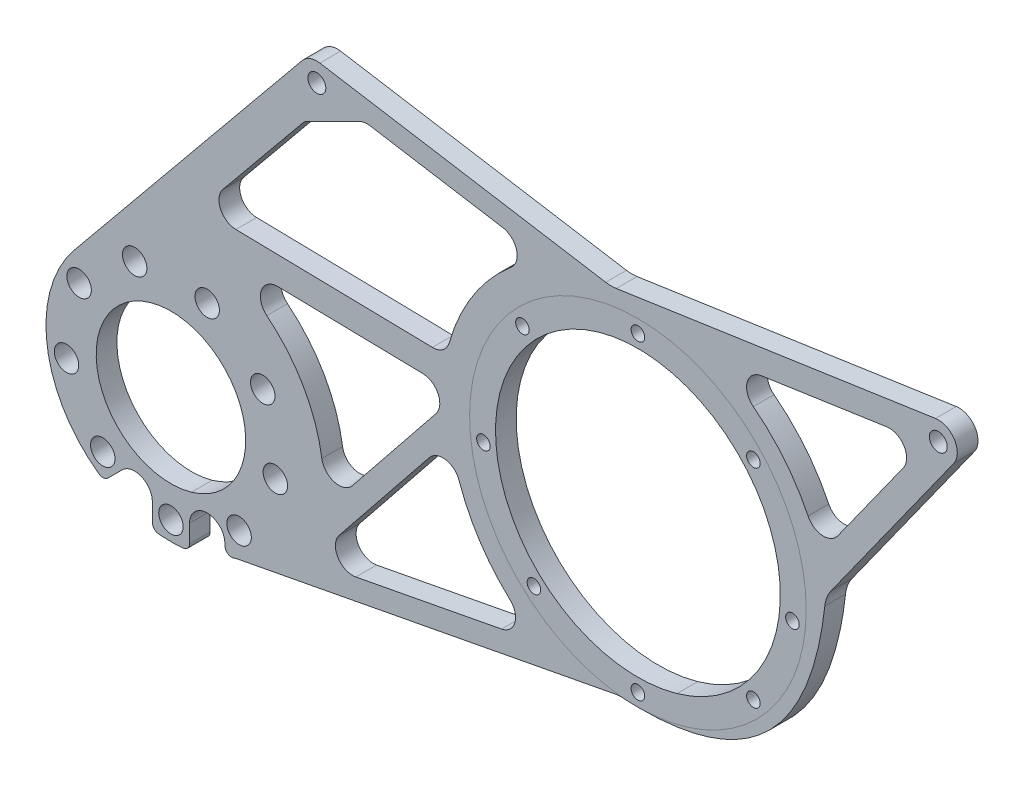
SolidWorks part; units mm, degrees
material "6061-T6 (SS)"
ref_plane "X-Y Datum" through (0, 0, 0) normal (0, 0, 1) x (1, 0, 0)
ref_plane "X-Z Datum" through (0, 0, 0) normal (0, 1, 0) x (1, 0, 0)
ref_plane "Y-Z Datum" through (0, 0, 0) normal (1, 0, 0) x (0, 0, -1)
sketch "Sketch15" plane through (0, 0, 0) normal (0, 0, 1) x (-1, 0, 0)
  line L0 (-666.75, 77.9015) -> (-548.64, 0) construction
  line L1 (-666.75, 77.9015) -> (-494.9785, 127) construction
  line L8 (-471.7786, 164.3167) -> (-477.0435, 159.0518)
  line L9 (-488.1397, 163.648) -> (-488.1397, 170.2207)
  line L10 (-501.8173, 170.2207) -> (-501.8173, 163.648)
  line L11 (-514.8173, 163.648) -> (-514.8173, 164.225)
  line L17 (-660.4, 0) -> (-548.64, 0)
  line L18 (-777.24, 0) -> (-660.4, 0)
  line L19 (-777.24, 145.034) -> (-777.24, 0)
  line L20 (-789.94, 132.334) -> (-764.54, 157.734)
  line L21 (-789.94, 157.734) -> (-764.54, 132.334)
  line L22 (-789.94, 132.334) -> (-764.54, 132.334)
  line L23 (-789.94, 157.734) -> (-764.54, 157.734)
  line L24 (-789.94, 157.734) -> (-789.94, 132.334)
  line L25 (-764.54, 157.734) -> (-764.54, 132.334)
  line L26 (-543.2372, -4.4272) -> (-459.4185, 97.8608)
  line L27 (-777.24, -6.985) -> (-548.64, -6.985)
  line L28 (-784.225, 0) -> (-784.225, 145.034)
  line L29 (-776.4928, 151.9789) -> (-660.1268, 139.4587)
  line L30 (-660.1268, 139.4587) -> (-518.666, 166.4019)
  circle A1 centre (-666.75, 77.9015) radius 52.3875
  circle A4 centre (-548.64, 0) radius 12.7
  circle A5 centre (-777.24, 0) radius 12.7
  arc A16 (-518.666, 166.4019) -> (-468.5208, 164.5979) centre (-494.9785, 127) ccw
  arc A17 (-468.5208, 164.5979) -> (-471.7786, 164.3167) centre (-469.9826, 162.5207) ccw
  arc A18 (-488.1397, 163.648) -> (-477.0435, 159.0518) centre (-481.6397, 163.648) ccw
  arc A19 (-488.1397, 170.2207) -> (-490.4283, 172.7483) centre (-490.6797, 170.2207) ccw
  arc A20 (-490.4283, 172.7483) -> (-499.5287, 172.7483) centre (-494.9785, 127) ccw
  arc A21 (-499.5287, 172.7483) -> (-501.8173, 170.2207) centre (-499.2773, 170.2207) ccw
  arc A22 (-514.8173, 163.648) -> (-501.8173, 163.648) centre (-508.3173, 163.648) ccw
  arc A23 (-514.8173, 164.225) -> (-518.666, 166.4019) centre (-517.3573, 164.225) ccw
  circle A30 centre (-709.2207, 116.1423) radius 2.5
  circle A31 centre (-624.2793, 39.6607) radius 2.5
  circle A33 centre (-709.2207, 39.6607) radius 2.5
  circle A34 centre (-723.5869, 83.8753) radius 2.5
  circle A35 centre (-609.9131, 83.8753) radius 2.5
  circle A36 centre (-666.75, 20.7515) radius 2.5
  arc A40 (-666.75, 132.5515) -> (-666.75, 137.5515) centre (-666.75, 135.0515) ccw
  arc A41 (-666.75, 137.5515) -> (-666.75, 132.5515) centre (-666.75, 135.0515) ccw
  circle A43 centre (-628.5092, 120.3722) radius 2.5
  circle A45 centre (-666.75, 77.9015) radius 61.9125
  circle A46 centre (-548.64, 0) radius 3.3
  circle A47 centre (-777.24, 0) radius 3.3
  circle A48 centre (-777.24, 145.034) radius 3.3
  circle A49 centre (-548.64, 0) radius 6.985
  circle A50 centre (-777.24, 0) radius 6.985
  circle A51 centre (-777.24, 145.034) radius 6.985
  circle A61 centre (-461.2035, 107.5) radius 4.5
  circle A62 centre (-481.6397, 90.352) radius 4.5
  circle A63 centre (-508.3173, 90.352) radius 4.5
  circle A64 centre (-528.7535, 107.5) radius 4.5
  circle A65 centre (-533.386, 133.7723) radius 4.5
  circle A66 centre (-520.0472, 156.8757) radius 4.5
  circle A67 centre (-494.9785, 166) radius 4.5
  circle A68 centre (-469.9098, 156.8757) radius 4.5
  circle A69 centre (-456.571, 133.7723) radius 4.5
  circle A71 centre (-494.9785, 127) radius 27.4955
  dimension "D2" = 6.6
  dimension "D3" = 6.6
  dimension "D4" = 6.6
  dimension "D5" = 13.97
  dimension "D6" = 13.97
  dimension "D7" = 13.97
  dimension "D1" = 141.4871
extrude "Boss-Extrude1" add sketch "Sketch15" along normal blind 7.62 contours A45 A1 A30 A31 A33 A34 A35 A36 A41 A40 A43 | L30 A45 L29 L25 L22 L19 A5 L18 L17 A4 L26 A16 | A51 L21 L25 L29 L20 | A51 L19 L22 L21 | L19 A51 L21 A48 | L20 A51 L19 A48 | A51 L28 L20 | A51 L20 L28 L22 L19 | L21 A51 L20 A48 | A51 L20 A48 L21 | L20 A51 L21 A48 | A51 L20 L29 | A5 L19 L22 L28 | A50 L19 A5 L28 | A50 L18 A5 L19 | A50 L27 A5 L18 | A50 L18 A47 L19 | L18 A50 L19 A47 | A5 L27 A4 L17 L18 | A49 L17 A4 L27 | A49 L26 A4 L17 | A49 A46 | L11 A23 A16 A17 L8 A18 L9 A19 A20 A21 L10 A22 A71 A69 A68 A67 A66 A65 A64 A63 A62 A61 region at (470.0892, -163.7557, 0) region at (621.9919, -118.1022, 0) region at (500.7414, -53.0926, 0) region at (540.1092, 0.1341, 0) region at (545.7357, 6.1347, 0) region at (662.94, 3.5042, 0) region at (557.2397, 3.7525, 0) region at (767.6155, -143.202, 0) region at (768.6403, 3.7525, 0) region at (770.798, -6.442, 0) region at (772.2286, -135.2354, 0) region at (772.7928, -151.1055, 0) region at (782.0394, 4.7994, 0) region at (780.9925, -8.5997, 0) region at (780.7424, -72.1789, 0) region at (773.8261, -3.4139, 0) region at (775.2402, -140.206, 0) region at (772.412, -145.034, 0) region at (780.8486, -135.5958, 0) region at (777.24, -149.862, 0) region at (782.068, -145.034, 0) region at (779.2398, -140.206, 0) region at (783.5955, -140.54, 0)
ref_point "Point1"
ref_point "Point2"
ref_plane "Plane1" through (666.75, -77.9015, 0) normal (-0.9615, -0.2748, 0) x (0, 0, 1)
ref_plane "Plane2" through (494.9785, -127, 0) normal (0.9615, 0.2748, 0) x (0, 0, -1)
split line "Split Line1"
split line "Split Line2"
sketch "Sketch17" plane through (0, 0, 7.62) normal (0, 0, 1) x (1, 0, 0)
  circle A0 centre (666.75, -77.9015) radius 61.9125 construction
  circle A1 centre (666.75, -77.9015) radius 61.9125
split line "Split Line3"
ref_axis "Axis4" through (666.75, -77.9015, 7.62) along (0, 0, -1)
ref_axis "Axis5" through (494.9785, -127, 7.62) along (0, 0, -1)
sketch "Sketch18" plane through (0, 0, 7.62) normal (0, 0, 1) x (1, 0, 0)
  line L4 (514.8173, -163.648) -> (514.8173, -164.225)
  line L5 (501.8173, -170.2207) -> (501.8173, -163.648)
  line L6 (488.1397, -163.648) -> (488.1397, -170.2207)
  line L7 (471.7786, -164.3167) -> (477.0435, -159.0518)
  line L8 (514.8173, -163.648) -> (514.8173, -164.225)
  line L9 (501.8173, -170.2207) -> (501.8173, -163.648)
  line L10 (488.1397, -163.648) -> (488.1397, -170.2207)
  line L11 (471.7786, -164.3167) -> (477.0435, -159.0518)
  line L12 (735.8271, -69.9563) -> (782.9228, -4.0616)
  line L13 (735.8271, -69.9563) -> (783.0611, -141.1732)
  line L14 (776.2216, 6.9104) -> (656.8438, -10.6825)
  line L15 (656.8438, -10.6825) -> (549.7714, 6.8928)
  line L16 (776.4928, -151.9789) -> (687.9549, -142.4528)
  line L17 (776.4928, -151.9789) -> (660.1268, -139.4587) construction
  line L18 (543.2372, 4.4272) -> (459.4185, -97.8608) construction
  line L19 (543.2372, 4.4272) -> (459.4185, -97.8608)
  line L20 (660.1268, -139.4587) -> (518.666, -166.4019) construction
  line L21 (660.1268, -139.4587) -> (518.666, -166.4019)
  circle A0 centre (666.75, -77.9015) radius 67.945
  circle A1 centre (666.75, -77.9015) radius 52.3875
  circle A2 centre (666.75, -77.9015) radius 52.3875
  circle A3 centre (548.64, 0) radius 12.7
  circle A4 centre (548.64, 0) radius 12.7
  circle A5 centre (777.24, 0) radius 12.7
  circle A6 centre (777.24, 0) radius 12.7
  circle A7 centre (777.24, 0) radius 6.985 construction
  circle A8 centre (777.24, -145.034) radius 6.985 construction
  circle A9 centre (548.64, 0) radius 6.985 construction
  arc A10 (514.8173, -164.225) -> (518.666, -166.4019) centre (517.3573, -164.225) ccw
  arc A11 (514.8173, -163.648) -> (501.8173, -163.648) centre (508.3173, -163.648) ccw
  arc A12 (499.5287, -172.7483) -> (501.8173, -170.2207) centre (499.2773, -170.2207) ccw
  arc A13 (490.4283, -172.7483) -> (499.5287, -172.7483) centre (494.9785, -127) ccw
  arc A14 (488.1397, -170.2207) -> (490.4283, -172.7483) centre (490.6797, -170.2207) ccw
  arc A15 (488.1397, -163.648) -> (477.0435, -159.0518) centre (481.6397, -163.648) ccw
  arc A16 (468.5208, -164.5979) -> (471.7786, -164.3167) centre (469.9826, -162.5207) ccw
  arc A17 (518.666, -166.4019) -> (468.5208, -164.5979) centre (494.9785, -127) ccw
  arc A18 (514.8173, -164.225) -> (518.666, -166.4019) centre (517.3573, -164.225) ccw
  arc A19 (514.8173, -163.648) -> (501.8173, -163.648) centre (508.3173, -163.648) ccw
  arc A20 (499.5287, -172.7483) -> (501.8173, -170.2207) centre (499.2773, -170.2207) ccw
  arc A21 (490.4283, -172.7483) -> (499.5287, -172.7483) centre (494.9785, -127) ccw
  arc A22 (488.1397, -170.2207) -> (490.4283, -172.7483) centre (490.6797, -170.2207) ccw
  arc A23 (488.1397, -163.648) -> (477.0435, -159.0518) centre (481.6397, -163.648) ccw
  arc A24 (468.5208, -164.5979) -> (471.7786, -164.3167) centre (469.9826, -162.5207) ccw
  arc A25 (518.666, -166.4019) -> (468.5208, -164.5979) centre (494.9785, -127) ccw
  circle A26 centre (777.24, -145.034) radius 6.985
  circle A27 centre (777.24, 0) radius 6.985
  circle A28 centre (548.64, 0) radius 6.985
  circle A29 centre (666.75, -77.9015) radius 69.5325
  circle A30 centre (666.75, -77.9015) radius 61.9125 construction
  point P56 (735.8271, -69.9563)
  line M37 (784.225, -145.034) -> (784.225, 0)
  line M39 (777.24, 6.985) -> (548.64, 6.985)
  dimension "D5" = 135.89
  dimension "D7" = 7.62
  dimension "D6" = 69.9563
  dimension "D1" = 0
  dimension "D2" = 0
  dimension "D3" = 0
  dimension "D4" = 0
extrude "Profile" cut sketch "Sketch18" against normal through all contours A6 A4 L15 L14 M39 | A28 L15 A4 M39 | A27 A6 L14 M39 | A26 A6 L12 L13 M37 | A27 L12 A6 M37 | L14 A29 L15 region at (660.8946, -9.368, 7.62) region at (660.9592, 1.1518, 7.62) region at (556.2469, 6.3803, 7.62) region at (769.684, 6.4437, 7.62) region at (767.9562, -72.3588, 7.62) region at (781.6609, -8.7245, 7.62)
fillet "Prof Fillet" radius 12.7 2 edges at (660.1268, -139.4587, 3.81) (656.8438, -10.6825, 3.81)
sketch "Sketch19" plane through (0, 0, 7.62) normal (0, 0, 1) x (1, 0, 0)
  line L0 (733.3947, -58.0707) -> (773.0846, -2.538)
  line L1 (773.0846, -2.538) -> (694.453, -14.126)
  line L2 (776.2216, 6.9104) -> (658.8007, -10.3941) construction
  line L3 (735.8271, -69.9563) -> (782.9228, -4.0616) construction
  line L4 (514.8173, -163.648) -> (514.8173, -164.225)
  line L5 (501.8173, -170.2207) -> (501.8173, -163.648)
  line L6 (488.1397, -163.648) -> (488.1397, -170.2207)
  line L7 (471.7786, -164.3167) -> (477.0435, -159.0518)
  line L8 (514.8173, -163.648) -> (514.8173, -164.225)
  line L9 (501.8173, -170.2207) -> (501.8173, -163.648)
  line L10 (488.1397, -163.648) -> (488.1397, -170.2207)
  line L11 (471.7786, -164.3167) -> (477.0435, -159.0518)
  line L12 (735.5557, -87.9288) -> (772.6812, -143.9048)
  line L13 (772.6812, -143.9048) -> (704.1334, -136.5295)
  line L14 (735.8271, -69.9563) -> (783.0611, -141.1732) construction
  line L15 (776.4928, -151.9789) -> (660.1268, -139.4587) construction
  arc A0 (694.453, -14.126) -> (733.3947, -58.0707) centre (666.75, -77.9015) cw
  circle A1 centre (666.75, -77.9015) radius 52.3875
  circle A2 centre (666.75, -77.9015) radius 52.3875
  circle A3 centre (548.64, 0) radius 12.7
  circle A4 centre (548.64, 0) radius 12.7
  circle A5 centre (777.24, 0) radius 12.7
  circle A6 centre (777.24, 0) radius 12.7
  circle A7 centre (666.75, -77.9015) radius 61.9125 construction
  arc A8 (704.1334, -136.5295) -> (735.5557, -87.9288) centre (666.75, -77.9015) ccw
  arc A10 (514.8173, -164.225) -> (518.666, -166.4019) centre (517.3573, -164.225) ccw
  arc A11 (514.8173, -163.648) -> (501.8173, -163.648) centre (508.3173, -163.648) ccw
  arc A12 (499.5287, -172.7483) -> (501.8173, -170.2207) centre (499.2773, -170.2207) ccw
  arc A13 (490.4283, -172.7483) -> (499.5287, -172.7483) centre (494.9785, -127) ccw
  arc A14 (488.1397, -170.2207) -> (490.4283, -172.7483) centre (490.6797, -170.2207) ccw
  arc A15 (488.1397, -163.648) -> (477.0435, -159.0518) centre (481.6397, -163.648) ccw
  arc A16 (468.5208, -164.5979) -> (471.7786, -164.3167) centre (469.9826, -162.5207) ccw
  arc A17 (518.666, -166.4019) -> (468.5208, -164.5979) centre (494.9785, -127) ccw
  arc A18 (514.8173, -164.225) -> (518.666, -166.4019) centre (517.3573, -164.225) ccw
  arc A19 (514.8173, -163.648) -> (501.8173, -163.648) centre (508.3173, -163.648) ccw
  arc A20 (499.5287, -172.7483) -> (501.8173, -170.2207) centre (499.2773, -170.2207) ccw
  arc A21 (490.4283, -172.7483) -> (499.5287, -172.7483) centre (494.9785, -127) ccw
  arc A22 (488.1397, -170.2207) -> (490.4283, -172.7483) centre (490.6797, -170.2207) ccw
  arc A23 (488.1397, -163.648) -> (477.0435, -159.0518) centre (481.6397, -163.648) ccw
  arc A24 (468.5208, -164.5979) -> (471.7786, -164.3167) centre (469.9826, -162.5207) ccw
  arc A25 (518.666, -166.4019) -> (468.5208, -164.5979) centre (494.9785, -127) ccw
  dimension "D7" = 7.62
  dimension "D8" = 7.62
  dimension "D5" = 8.89
  dimension "D6" = 8.89
  dimension "D9" = 10.16
  dimension "D10" = 7.62
  dimension "D1" = 0
  dimension "D2" = 0
  dimension "D3" = 0
  dimension "D4" = 0
extrude "Cut-Extrude2" cut sketch "Sketch19" against normal through all contours L1 A0 L0 | A8 L13 L12 | L1 A6 L0 | L13 A8 L12 region at (735.848, -23.7543, 7.62) region at (768.7055, -5.2125, 7.62) region at (739.9333, -124.2564, 7.62)
fillet "Fillet2" radius 6.35 6 edges at (694.453, -14.126, 3.81) (773.0846, -2.538, 3.81) (733.3947, -58.0707, 3.81) (772.6812, -143.9048, 3.81) (704.1334, -136.5295, 3.81) (735.5557, -87.9288, 3.81)
sketch "Sketch22" plane through (0, 0, 7.62) normal (0, 0, 1) x (1, 0, 0)
  line L0 (632.6117, -14.4269) -> (566.1379, -3.5157)
  line L1 (566.1379, -3.5157) -> (544.2067, -14.4269)
  line L2 (654.892, -10.3621) -> (549.7714, 6.8928) construction
  line L4 (514.8173, -163.648) -> (514.8173, -164.225)
  line L5 (501.8173, -170.2207) -> (501.8173, -163.648)
  line L6 (488.1397, -163.648) -> (488.1397, -170.2207)
  line L7 (471.7786, -164.3167) -> (477.0435, -159.0518)
  line L8 (514.8173, -163.648) -> (514.8173, -164.225)
  line L9 (501.8173, -170.2207) -> (501.8173, -163.648)
  line L10 (488.1397, -163.648) -> (488.1397, -170.2207)
  line L11 (471.7786, -164.3167) -> (477.0435, -159.0518)
  line L12 (630.6345, -137.319) -> (546.093, -153.4211)
  line L13 (546.093, -153.4211) -> (598.0511, -88.6361)
  line L14 (658.2707, -139.8122) -> (518.666, -166.4019) construction
  line L15 (505.7956, -61.3018) -> (544.2067, -14.4269)
  line L16 (544.2067, -14.4269) -> (632.6117, -14.4269)
  line L17 (596.2144, -63.0967) -> (505.7956, -61.3018)
  line L18 (543.2372, 4.4272) -> (459.4185, -97.8608) construction
  line L19 (502.7234, -71.4029) -> (600.5471, -73.3447)
  line L20 (600.5471, -73.3447) -> (550.4088, -135.8605)
  arc A0 (598.0511, -88.6361) -> (630.6345, -137.319) centre (666.75, -77.9015) ccw
  circle A1 centre (666.75, -77.9015) radius 52.3875
  circle A2 centre (666.75, -77.9015) radius 52.3875
  circle A3 centre (548.64, 0) radius 12.7
  circle A4 centre (548.64, 0) radius 12.7
  circle A5 centre (777.24, 0) radius 12.7
  circle A6 centre (777.24, 0) radius 12.7
  circle A7 centre (666.75, -77.9015) radius 61.9125 construction
  arc A8 (632.6117, -14.4269) -> (596.2144, -63.0967) centre (666.75, -77.9015) ccw
  arc A9 (502.7234, -71.4029) -> (550.4088, -135.8605) centre (494.9785, -127) cw
  arc A10 (514.8173, -164.225) -> (518.666, -166.4019) centre (517.3573, -164.225) ccw
  arc A11 (514.8173, -163.648) -> (501.8173, -163.648) centre (508.3173, -163.648) ccw
  arc A12 (499.5287, -172.7483) -> (501.8173, -170.2207) centre (499.2773, -170.2207) ccw
  arc A13 (490.4283, -172.7483) -> (499.5287, -172.7483) centre (494.9785, -127) ccw
  arc A14 (488.1397, -170.2207) -> (490.4283, -172.7483) centre (490.6797, -170.2207) ccw
  arc A15 (488.1397, -163.648) -> (477.0435, -159.0518) centre (481.6397, -163.648) ccw
  arc A16 (468.5208, -164.5979) -> (471.7786, -164.3167) centre (469.9826, -162.5207) ccw
  arc A17 (518.666, -166.4019) -> (468.5208, -164.5979) centre (494.9785, -127) ccw
  arc A18 (514.8173, -164.225) -> (518.666, -166.4019) centre (517.3573, -164.225) ccw
  arc A19 (514.8173, -163.648) -> (501.8173, -163.648) centre (508.3173, -163.648) ccw
  arc A20 (499.5287, -172.7483) -> (501.8173, -170.2207) centre (499.2773, -170.2207) ccw
  arc A21 (490.4283, -172.7483) -> (499.5287, -172.7483) centre (494.9785, -127) ccw
  arc A22 (488.1397, -170.2207) -> (490.4283, -172.7483) centre (490.6797, -170.2207) ccw
  arc A23 (488.1397, -163.648) -> (477.0435, -159.0518) centre (481.6397, -163.648) ccw
  arc A24 (468.5208, -164.5979) -> (471.7786, -164.3167) centre (469.9826, -162.5207) ccw
  arc A25 (518.666, -166.4019) -> (468.5208, -164.5979) centre (494.9785, -127) ccw
  dimension "D6" = 7.62
  dimension "D7" = 10.16
  dimension "D14" = 10.16
  dimension "D5" = 7.62
  dimension "D8" = 12.7
  dimension "D9" = 7.62
  dimension "D10" = 24.4955
  dimension "D11" = 90.4189
  dimension "D12" = 51.9581
  dimension "D13" = 64.7849
  dimension "D15" = 10.16
  dimension "D16" = 7.62
  dimension "D17" = 1.7949
  dimension "D1" = 0
  dimension "D2" = 0
  dimension "D3" = 0
  dimension "D4" = 0
extrude "Cut-Extrude4" cut sketch "Sketch22" against normal through all contours L1 L16 L0 | L1 A4 | L17 L15 L16 A8 | L20 A9 L19 | L13 A0 L12 region at (581.8773, -10.8016, 7.62) region at (553.8291, -10.4299, 7.62)
fillet "Fillet5" radius 6.35 11 edges at (630.6345, -137.319, 3.81) (546.093, -153.4211, 3.81) (598.0511, -88.6361, 3.81) (550.4088, -135.8605, 3.81) (600.5471, -73.3447, 3.81) (502.7234, -71.4029, 3.81) (596.2144, -63.0967, 3.81) (505.7956, -61.3018, 3.81) (632.6117, -14.4269, 3.81) (566.1379, -3.5157, 3.81) (544.2067, -14.4269, 3.81)
sketch "Sketch26" plane through (0, 0, 7.62) normal (0, 0, 1) x (1, 0, 0)
  line L0 (776.4928, -151.9789) -> (662.0055, -139.6608) construction
  line L1 (735.8271, -69.9563) -> (783.0611, -141.1732) construction
  line L2 (772.6812, -143.9048) -> (735.5557, -87.9288)
  line L3 (704.1334, -136.5295) -> (772.6812, -143.9048)
  line L4 (488.1397, -163.648) -> (488.1397, -170.2207)
  line L5 (501.8173, -170.2207) -> (501.8173, -163.648)
  line L6 (514.8173, -163.648) -> (514.8173, -164.225)
  line L7 (471.7786, -164.3167) -> (477.0435, -159.0518)
  line L8 (488.1397, -163.648) -> (488.1397, -170.2207)
  line L9 (501.8173, -170.2207) -> (501.8173, -163.648)
  line L10 (514.8173, -163.648) -> (514.8173, -164.225)
  line L11 (471.7786, -164.3167) -> (477.0435, -159.0518)
  line L12 (772.6812, -143.9048) -> (735.5557, -87.9288)
  line L13 (704.1334, -136.5295) -> (772.6812, -143.9048)
  line L14 (733.3947, -58.0707) -> (773.0846, -2.538)
  line L15 (773.0846, -2.538) -> (694.453, -14.126)
  line L16 (733.3947, -58.0707) -> (773.0846, -2.538)
  line L17 (773.0846, -2.538) -> (694.453, -14.126)
  line L18 (776.4928, -151.9789) -> (662.0055, -139.6608)
  line L19 (735.8271, -69.9563) -> (783.0611, -141.1732)
  circle A1 centre (666.75, -77.9015) radius 52.3875
  circle A2 centre (666.75, -77.9015) radius 52.3875
  circle A3 centre (777.24, 0) radius 12.7
  circle A4 centre (777.24, 0) radius 12.7
  circle A5 centre (548.64, 0) radius 12.7
  circle A6 centre (548.64, 0) radius 12.7
  arc A7 (704.1334, -136.5295) -> (735.5557, -87.9288) centre (666.75, -77.9015) ccw
  arc A8 (704.1334, -136.5295) -> (735.5557, -87.9288) centre (666.75, -77.9015) ccw
  arc A9 (733.3947, -58.0707) -> (694.453, -14.126) centre (666.75, -77.9015) ccw
  arc A10 (733.3947, -58.0707) -> (694.453, -14.126) centre (666.75, -77.9015) ccw
  circle A11 centre (666.75, -77.9015) radius 69.5325
  arc A12 (776.4928, -151.9789) -> (783.0611, -141.1732) centre (777.24, -145.034) ccw construction
  arc A13 (776.4928, -151.9789) -> (783.0611, -141.1732) centre (777.24, -145.034) ccw
  arc A14 (488.1397, -170.2207) -> (490.4283, -172.7483) centre (490.6797, -170.2207) ccw
  arc A15 (490.4283, -172.7483) -> (499.5287, -172.7483) centre (494.9785, -127) ccw
  arc A16 (499.5287, -172.7483) -> (501.8173, -170.2207) centre (499.2773, -170.2207) ccw
  arc A17 (514.8173, -163.648) -> (501.8173, -163.648) centre (508.3173, -163.648) ccw
  arc A18 (514.8173, -164.225) -> (518.666, -166.4019) centre (517.3573, -164.225) ccw
  arc A19 (518.666, -166.4019) -> (468.5208, -164.5979) centre (494.9785, -127) ccw
  arc A20 (468.5208, -164.5979) -> (471.7786, -164.3167) centre (469.9826, -162.5207) ccw
  arc A21 (488.1397, -163.648) -> (477.0435, -159.0518) centre (481.6397, -163.648) ccw
  arc A22 (488.1397, -170.2207) -> (490.4283, -172.7483) centre (490.6797, -170.2207) ccw
  arc A23 (490.4283, -172.7483) -> (499.5287, -172.7483) centre (494.9785, -127) ccw
  arc A24 (499.5287, -172.7483) -> (501.8173, -170.2207) centre (499.2773, -170.2207) ccw
  arc A25 (514.8173, -163.648) -> (501.8173, -163.648) centre (508.3173, -163.648) ccw
  arc A26 (514.8173, -164.225) -> (518.666, -166.4019) centre (517.3573, -164.225) ccw
  arc A27 (518.666, -166.4019) -> (468.5208, -164.5979) centre (494.9785, -127) ccw
  arc A28 (468.5208, -164.5979) -> (471.7786, -164.3167) centre (469.9826, -162.5207) ccw
  arc A29 (488.1397, -163.648) -> (477.0435, -159.0518) centre (481.6397, -163.648) ccw
  spline S0 degree 2 poles (662.0055, -139.6608) (729.1997, -143.0989) (735.8271, -69.9563) knots 0 0 0 1 1 1
  dimension "D7" = 115.4464
  dimension "D8" = 44.8387
  dimension "D1" = 0
  dimension "D2" = 0
  dimension "D3" = 0
  dimension "D4" = 0
  dimension "D5" = 0
  dimension "D6" = 0
extrude "Cut-Extrude8" cut sketch "Sketch26" against normal through all contours L18 A13 L19 A11 L12 L13 | A8 L13 L12 | S0 L18 A11 A8 region at (739.9333, -124.2564, 7.62) region at (755.1498, -115.2328, 7.62) region at (724.2673, -115.0887, 7.62)
fillet "Fillet6" radius 12.7 1 edges at (735.8271, -69.9563, 3.81)
